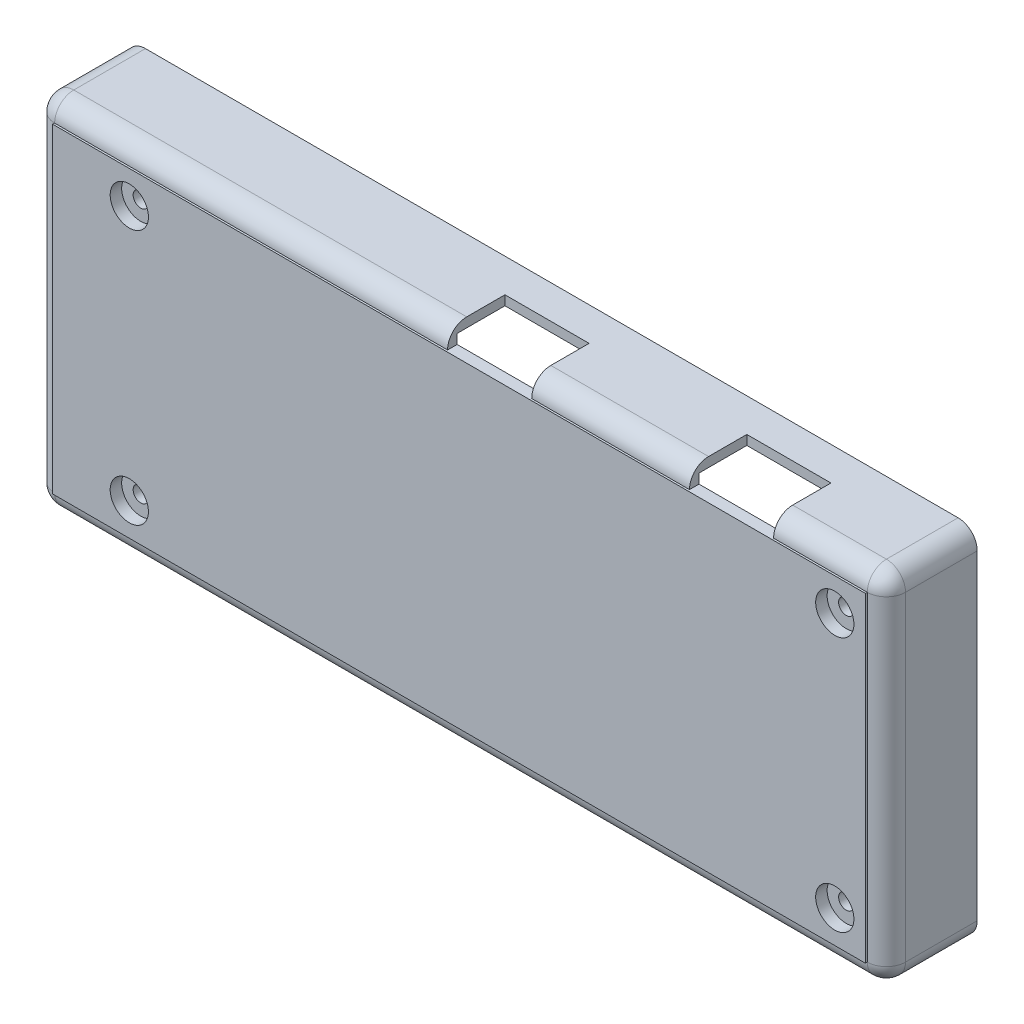
SolidWorks part; units mm, degrees
ref_plane "前视基准面" through (0, 0, 0) normal (0, 0, 1) x (1, 0, 0)
ref_plane "上视基准面" through (0, 0, 0) normal (0, 1, 0) x (1, 0, 0)
ref_plane "右视基准面" through (0, 0, 0) normal (1, 0, 0) x (0, 0, -1)
sketch "草图2" plane through (0, 0, 0) normal (0, 0, 1) x (1, 0, 0)
  line L0 (0, 0) -> (85, 0)
  line L5 (-2, 2) -> (-2, 35.5)
  line L10 (0, 37.5) -> (85, 37.5)
  line L15 (87, 35.5) -> (87, 2)
  arc A0 (0, 0) -> (-2, 2) centre (0, 2) cw
  arc A1 (-2, 35.5) -> (0, 37.5) centre (0, 35.5) cw
  arc A2 (87, 35.5) -> (85, 37.5) centre (85, 35.5) ccw
  arc A3 (85, 0) -> (87, 2) centre (85, 2) ccw
  dimension "D11" = 2
  dimension "D2" = 2
  dimension "D3" = 2
  dimension "D16" = 85
  dimension "D10" = 2
  dimension "D4" = 2
  dimension "D5" = 33.5
  dimension "D6" = 2
  dimension "D7" = 33.5
  dimension "D8" = 2
  dimension "D9" = 2
  dimension "D12" = 2
  dimension "D13" = 2
  dimension "D14" = 2
  dimension "D15" = 2
extrude "凸台-拉伸1" add sketch "草图2" along normal blind 9.5 contours L15 A3 L0 A0 L5 A1 L10 A2
sketch "草图3" plane through (0, 0, 0) normal (0, 0, -1) x (-1, 0, 0)
  line L0 (-83, 2) -> (-2.009, 2)
  line L1 (0, 0) -> (-85, 0) construction
  line L7 (-85, 4) -> (-85, 33.5)
  line L13 (-83, 35.5) -> (-2.009, 35.5)
  line L19 (-0.009, 33.5) -> (-0.009, 4)
  line L20 (2, 2) -> (2, 35.5) construction
  line L26 (0, 37.5) -> (-85, 37.5) construction
  line L27 (-87, 35.5) -> (-87, 2) construction
  arc A0 (-85, 4) -> (-83, 2) centre (-83, 4) ccw
  arc A1 (-83, 35.5) -> (-85, 33.5) centre (-83, 33.5) ccw
  arc A2 (-2.009, 35.5) -> (-0.009, 33.5) centre (-2.009, 33.5) cw
  arc A3 (-2.009, 2) -> (-0.009, 4) centre (-2.009, 4) ccw
  dimension "D4" = 2
  dimension "D9" = 2
  dimension "D12" = 2
  dimension "D13" = 2
  dimension "D14" = 2
  dimension "D16" = 2
  dimension "D17" = 2
  dimension "D2" = 2.009
  dimension "D3" = 2
  dimension "D5" = 2
  dimension "D6" = 2
  dimension "D7" = 2
  dimension "D8" = 2
  dimension "D10" = 2
  dimension "D11" = 2
  dimension "D15" = 2
extrude "切除-拉伸1" cut sketch "草图3" against normal blind 8.5
sketch "草图4" plane through (0, 0, 8.5) normal (0, 0, -1) x (-1, 0, 0)
  line L0 (-2.009, 35.5) -> (-83, 35.5) construction
  line L1 (-85, 33.5) -> (-85, 4) construction
  line L2 (-0.009, 4) -> (-0.009, 33.5) construction
  line L3 (-83, 2) -> (-2.009, 2) construction
  line L4 (-83, 2) -> (-2.009, 2) construction
  line L5 (-0.009, 4) -> (-0.009, 33.5) construction
  line L6 (-33.009, 35.5) -> (-23.009, 35.5)
  line L7 (-33.009, 35.5) -> (-33.009, 33.5)
  line L8 (-33.009, 33.5) -> (-23.009, 33.5)
  line L9 (-23.009, 35.5) -> (-23.009, 33.5)
  line L10 (-65, 2) -> (-60, 2)
  line L11 (-65, 2) -> (-65, 4)
  line L12 (-65, 4) -> (-60, 4)
  line L13 (-60, 2) -> (-60, 4)
  line L14 (-85, 33.5) -> (-85, 4) construction
  circle A0 centre (-81.8, 32.1) radius 2.5
  circle A1 centre (-8.009, 32.1) radius 2.5
  circle A2 centre (-8.009, 5.4) radius 2.5
  circle A3 centre (-81.8, 5.4) radius 2.5
  point P28 (-65, 3)
  dimension "D1" = 5
  dimension "D6" = 8
  dimension "D7" = 3.4
  dimension "D9" = 2
  dimension "D10" = 10
  dimension "D11" = 23
  dimension "D12" = 2
  dimension "D15" = 5
  dimension "D5" = 5
  dimension "D16" = 5
  dimension "D2" = 3.4
  dimension "D3" = 3.2
  dimension "D8" = 8
  dimension "D13" = 5
  dimension "D14" = 20
  dimension "D4" = 3.2
  dimension "D17" = 3.4
  dimension "D18" = 3.4
extrude "凸台-拉伸2" add sketch "草图4" along normal blind 5
sketch "草图5" plane through (0, 0, 3.5) normal (0, 0, -1) x (-1, 0, 0)
  circle A0 centre (-81.8, 32.1) radius 0.8
  dimension "D1" = 1.6
sketch "草图7" plane through (0, 0, 3.5) normal (0, 0, -1) x (-1, 0, 0)
  circle A0 centre (-8.009, 5.4) radius 0.8
  dimension "D1" = 1.6
sketch "草图6" plane through (0, 0, 3.5) normal (0, 0, -1) x (-1, 0, 0)
  circle A0 centre (-8.009, 32.1) radius 0.8
  dimension "D1" = 1.6
sketch "草图8" plane through (0, 0, 3.5) normal (0, 0, -1) x (-1, 0, 0)
  circle A0 centre (-81.8, 5.4) radius 0.8
  dimension "D1" = 1.6
sketch "草图10" plane through (0, 37.5, 0) normal (0, 1, 0) x (1, 0, 0)
  line L0 (0, 0) -> (85, 0) construction
  line L1 (49.9, -3.5) -> (41.1, -3.5)
  line L2 (49.9, -3.5) -> (49.9, -9.5)
  line L3 (49.9, -9.5) -> (41.1, -9.5)
  line L4 (41.1, -3.5) -> (41.1, -9.5)
  line L5 (0, -9.5) -> (85, -9.5) construction
  line L7 (66.4, -3.5) -> (75.2, -3.5)
  line L8 (66.4, -3.5) -> (66.4, -9.5)
  line L9 (66.4, -9.5) -> (75.2, -9.5)
  line L10 (75.2, -3.5) -> (75.2, -9.5)
  line L12 (85, -9.5) -> (85, 0) construction
  dimension "D1" = 16.5
  dimension "D2" = 8.8
  dimension "D3" = 9.8
  dimension "D4" = 8.8
  dimension "D5" = 3.5
  dimension "D6" = 3.5
extrude "切除-拉伸3" cut sketch "草图10" against normal blind 2
sketch "草图11" plane through (-2, 0, 0) normal (-1, 0, 0) x (0, 0, 1)
  line L5 (9.5, 35.5) -> (0, 35.5) construction
  line L6 (0, 2) -> (0, 35.5) construction
  line L8 (0, 20.35) -> (0, 17.15)
  arc A1 (0, 17.15) -> (0, 20.35) centre (0, 18.75) ccw
  dimension "D1" = 1.6
  dimension "D2" = 16.75
extrude "切除-拉伸4" cut sketch "草图11" against normal blind 3
fillet "圆角4" radius 2 9 edges at (80.1, 37.5, 9.5) (86.4142, 36.9142, 9.5) (87, 18.75, 9.5) (86.4142, 0.5858, 9.5) (42.5, 0, 9.5) (-1.4142, 0.5858, 9.5) (-2, 18.75, 9.5) (-1.4142, 36.9142, 9.5) (20.55, 37.5, 9.5)
fillet "圆角5" radius 2 1 edges at (58.15, 37.5, 9.5)
extrude "切除-拉伸5" cut sketch "草图5" against normal blind 10
extrude "切除-拉伸6" cut sketch "草图7" against normal blind 10
extrude "切除-拉伸7" cut sketch "草图6" against normal blind 10
extrude "切除-拉伸8" cut sketch "草图8" against normal blind 10
sketch "草图12" plane through (0, 0, 9.5) normal (0, 0, 1) x (1, 0, 0)
  circle A0 centre (8.009, 32.1) radius 2
  circle A1 centre (81.8, 32.1) radius 2
  circle A2 centre (81.8, 5.4) radius 2
  circle A3 centre (8.009, 5.4) radius 2
  dimension "D1" = 4
  dimension "D2" = 4
  dimension "D3" = 4
  dimension "D4" = 4
extrude "切除-拉伸9" cut sketch "草图12" against normal blind 1
sketch "草图14" plane through (0, 35.5, 0) normal (0, -1, 0) x (1, 0, 0)
  line L1 (49.9, 8.5) -> (51.4, 8.5)
  line L2 (49.9, 8.5) -> (49.9, 3.5)
  line L3 (49.9, 3.5) -> (51.4, 3.5)
  line L4 (51.4, 8.5) -> (51.4, 3.5)
  line L5 (66.4, 8.5) -> (64.9, 8.5)
  line L6 (66.4, 8.5) -> (66.4, 3.5)
  line L7 (66.4, 3.5) -> (64.9, 3.5)
  line L8 (64.9, 8.5) -> (64.9, 3.5)
  dimension "D1" = 1.5
  dimension "D2" = 5
  dimension "D3" = 1.5
  dimension "D4" = 5
extrude "切除-拉伸11" cut sketch "草图14" against normal blind 1
sketch "草图15" plane through (0, 35.5, 0) normal (0, -1, 0) x (1, 0, 0)
  line L1 (75.2, 8.5) -> (76.7, 8.5)
  line L2 (75.2, 8.5) -> (75.2, 3.5)
  line L3 (75.2, 3.5) -> (76.7, 3.5)
  line L4 (76.7, 8.5) -> (76.7, 3.5)
  dimension "D1" = 1.5
  dimension "D2" = 5
extrude "切除-拉伸12" cut sketch "草图15" against normal blind 1
sketch "草图16" plane through (0, 35.5, 0) normal (0, -1, 0) x (1, 0, 0)
  line L1 (41.1, 8.5) -> (39.6, 8.5)
  line L2 (41.1, 8.5) -> (41.1, 3.5)
  line L3 (41.1, 3.5) -> (39.6, 3.5)
  line L4 (39.6, 8.5) -> (39.6, 3.5)
  dimension "D1" = 1.5
  dimension "D2" = 5
extrude "切除-拉伸13" cut sketch "草图16" against normal blind 1
sketch "草图18" plane through (0, 0, 8.5) normal (0, 0, -1) x (-1, 0, 0)
  line L0 (-83, 2) -> (-65, 2) construction
  line L1 (-80, 11) -> (-77, 11)
  line L2 (-80, 11) -> (-80, 8)
  line L3 (-80, 8) -> (-77, 8)
  line L4 (-77, 11) -> (-77, 8)
  line L5 (-80, 29.5) -> (-77, 29.5)
  line L6 (-80, 29.5) -> (-80, 26.5)
  line L7 (-80, 26.5) -> (-77, 26.5)
  line L8 (-77, 29.5) -> (-77, 26.5)
  line L9 (-76.7, 35.5) -> (-83, 35.5) construction
  line L10 (-60, 2) -> (-2.009, 2) construction
  line L11 (-37.009, 25.5) -> (-33.009, 25.5)
  line L12 (-37.009, 25.5) -> (-37.009, 12)
  line L13 (-37.009, 12) -> (-33.009, 12)
  line L14 (-33.009, 25.5) -> (-33.009, 12)
  line L15 (-2.009, 35.5) -> (-83, 35.5) construction
  line L16 (-0.009, 4) -> (-0.009, 33.5) construction
  line L17 (-85, 33.5) -> (-85, 4) construction
  dimension "D1" = 3
  dimension "D2" = 3
  dimension "D3" = 6
  dimension "D4" = 6
  dimension "D5" = 3
  dimension "D6" = 3
  dimension "D7" = 4
  dimension "D8" = 10
  dimension "D9" = 10
  dimension "D10" = 33
  dimension "D11" = 5
  dimension "D12" = 5
extrude "凸台-拉伸3" add sketch "草图18" along normal blind 5
sketch "草图19" plane through (0, 0, 0) normal (0, 0, -1) x (-1, 0, 0)
  line L29 (-85, 33.5) -> (-85, 4) construction
  line L30 (-84, 36.5) -> (-1.009, 36.5)
  line L31 (-86, 34.5) -> (-86, 3)
  line L32 (-84, 1) -> (-1.009, 1)
  line L35 (-2.009, 35.5) -> (-83, 35.5) construction
  line L37 (-83, 2) -> (-2.009, 2) construction
  line L38 (-0.009, 33.6) -> (-0.009, 20.35)
  line L39 (-83, 35.5) -> (-2.0065, 35.5)
  line L40 (-85, 33.5) -> (-85, 4)
  line L41 (-83, 2) -> (-2.0065, 2)
  line L43 (-0.009, 20.35) -> (0.9955, 20.35)
  line L44 (-0.009, 20.35) -> (2, 20.35) construction
  line L45 (0.9955, 20.35) -> (0.9885, 34.6)
  line L46 (-0.009, 17.15) -> (-0.009, 3.9)
  line L47 (-0.009, 17.15) -> (0.9955, 17.15)
  line L48 (-0.009, 17.15) -> (2, 17.15) construction
  line L49 (0.9955, 17.15) -> (0.9885, 2.9)
  arc A0 (-84, 36.5) -> (-86, 34.5) centre (-84, 34.5) ccw
  arc A1 (-86, 3) -> (-84, 1) centre (-84, 3) ccw
  arc A2 (-1.009, 36.5) -> (0.9885, 34.6) centre (-1.009, 34.5) cw
  arc A3 (-1.009, 1) -> (0.9885, 2.9) centre (-1.009, 3) ccw
  arc A4 (-83, 35.5) -> (-85, 33.5) centre (-83, 33.5) ccw
  arc A5 (-85, 4) -> (-83, 2) centre (-83, 4) ccw
  arc A6 (-2.0065, 2) -> (-0.009, 3.9) centre (-2.0065, 4) ccw
  arc A7 (-2.0065, 35.5) -> (-0.009, 33.6) centre (-2.0065, 33.5) cw
  dimension "D5" = 2
  dimension "D6" = 2
  dimension "D7" = 2
  dimension "D8" = 2
  dimension "D13" = 2
  dimension "D14" = 2
  dimension "D15" = 2
  dimension "D16" = 2
  dimension "D17" = 13.25
  dimension "D1" = 1
  dimension "D2" = 1
  dimension "D3" = 14.25
  dimension "D4" = 1
  dimension "D9" = 1
  dimension "D10" = 1
  dimension "D11" = 14.25
  dimension "D12" = 1
  dimension "D18" = 13.25
sketch "草图20" plane through (0, 35.5, 0) normal (0, -1, 0) x (1, 0, 0)
  line L0 (39.6, 3.5) -> (51.4, 3.5)
  line L5 (39.6, 3.5) -> (39.6, 2)
  line L6 (51.4, 3.5) -> (51.4, 2)
  line L7 (39.6, 2) -> (51.4, 2)
  line L9 (64.9, 3.5) -> (76.7, 3.5)
  line L10 (64.9, 3.5) -> (64.9, 2)
  line L11 (76.7, 3.5) -> (76.7, 2)
  line L12 (64.9, 2) -> (76.7, 2)
  dimension "D1" = 1.5
  dimension "D2" = 1.5
extrude "切除-拉伸16" cut sketch "草图20" against normal blind 1
sketch "草图21" plane through (0, 0, 9.5) normal (0, 0, 1) x (1, 0, 0)
  line L1 (0, 35.5) -> (85, 35.5)
  line L2 (0, 35.5) -> (0, 2)
  line L3 (0, 2) -> (85, 2)
  line L4 (85, 35.5) -> (85, 2)
  circle A0 centre (8.009, 32.1) radius 2
  circle A1 centre (8.009, 5.4) radius 2
  circle A2 centre (81.8, 32.1) radius 2
  circle A3 centre (81.8, 5.4) radius 2
  dimension "D1" = 4
  dimension "D2" = 4
  dimension "D3" = 4
  dimension "D4" = 4
extrude "凸台-拉伸4" add sketch "草图21" along normal blind 0.2
extrude "切除-拉伸17" cut sketch "草图19" against normal blind 1
sketch "草图22" plane through (0, 0, 1) normal (0, 0, -1) x (-1, 0, 0)
  line L0 (-2.009, 2) -> (-83, 2) construction
  line L1 (-25.5, 2) -> (-17.7, 2)
  line L2 (-25.5, 2) -> (-25.5, 1)
  line L3 (-25.5, 1) -> (-17.7, 1)
  line L4 (-17.7, 2) -> (-17.7, 1)
  line L5 (-84, 1) -> (-1.009, 1) construction
  line L6 (-87, 35.5) -> (-87, 2) construction
  dimension "D1" = 61.5
  dimension "D2" = 7.8
extrude "切除-拉伸18" cut sketch "草图22" against normal blind 1
